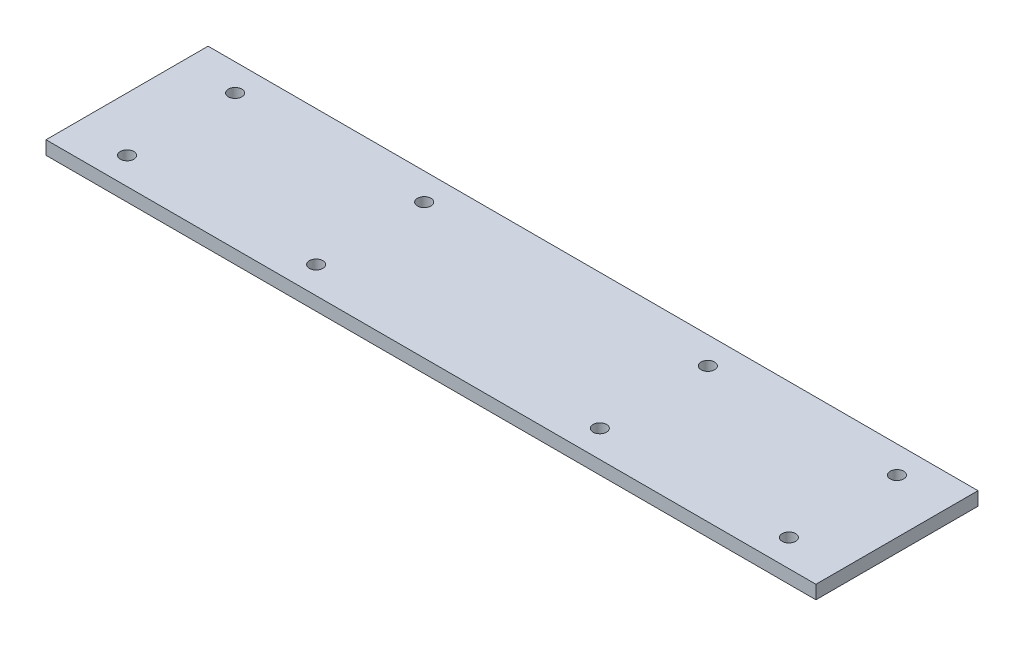
SolidWorks part; units mm, degrees
material "Cast Carbon Steel"
ref_plane "Front Plane" through (0, 0, 0) normal (0, 0, 1) x (1, 0, 0)
ref_plane "Top Plane" through (0, 0, 0) normal (0, 1, 0) x (1, 0, 0)
ref_plane "Right Plane" through (0, 0, 0) normal (1, 0, 0) x (0, 0, -1)
sketch "Sketch1" plane through (0, 0, 0) normal (0, 1, 0) x (1, 0, 0)
  line L1 (-295.5989, 152.4) -> (428.3011, 152.4)
  line L2 (-295.5989, 152.4) -> (-295.5989, 0)
  line L3 (-295.5989, 0) -> (428.3011, 0)
  line L4 (428.3011, 152.4) -> (428.3011, 0)
  point P5 (66.3511, 152.4)
  dimension "D1" = 723.9
  dimension "D2" = 152.4
  dimension "D3" = 152.4
  dimension "D4" = 295.5989
extrude "Boss-Extrude1" add sketch "Sketch1" along normal blind 12.7
sketch "Sketch2" plane through (0, 12.7, 0) normal (0, 1, 0) x (1, 0, 0)
  line L0 (428.3011, 0) -> (428.3011, 152.4) construction
  line L1 (66.3511, 152.4) -> (66.3511, 0) construction
  line L2 (428.3011, 152.4) -> (-295.5989, 152.4) construction
  line L3 (-295.5989, 0) -> (428.3011, 0) construction
  circle A0 centre (377.5011, 127) radius 6.35
  circle A1 centre (377.5011, 25.4) radius 6.35
  circle A2 centre (199.7011, 127) radius 6.35
  circle A3 centre (199.7011, 25.4) radius 6.35
  circle A4 centre (-244.7989, 127) radius 6.35
  circle A5 centre (-66.9989, 127) radius 6.35
  circle A6 centre (-244.7989, 25.4) radius 6.35
  circle A7 centre (-66.9989, 25.4) radius 6.35
  dimension "D1" = 12.7
  dimension "D2" = 12.7
  dimension "D3" = 12.7
  dimension "D4" = 12.7
  dimension "D5" = 50.8
  dimension "D6" = 25.4
  dimension "D8" = 177.8
  dimension "D9" = 101.6
extrude "Cut-Extrude1" cut sketch "Sketch2" against normal through all
